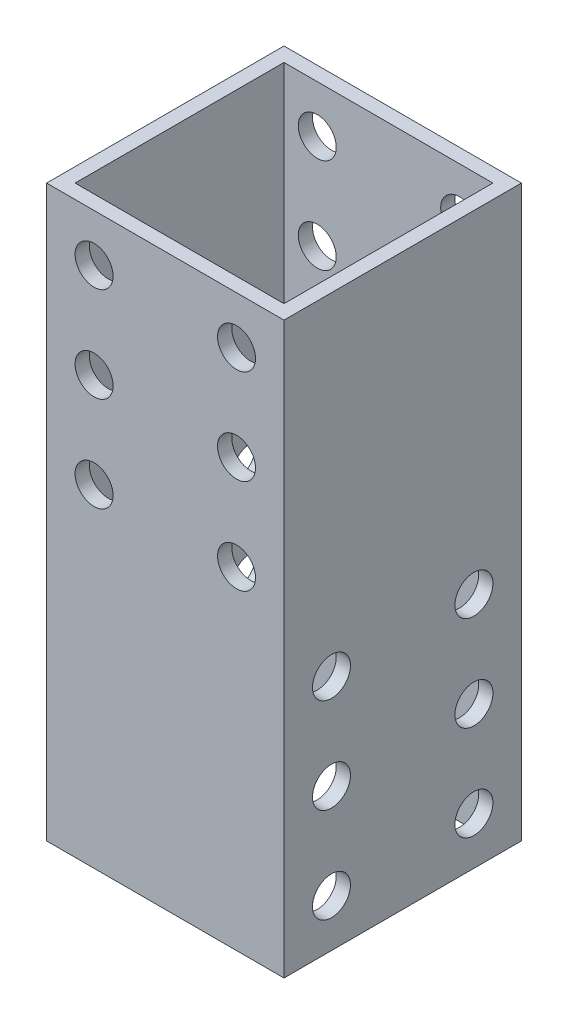
SolidWorks part; units mm, degrees
material "1060 Alloy"
ref_plane "Front Plane" through (0, 0, 0) normal (0, 0, 1) x (1, 0, 0)
ref_plane "Top Plane" through (0, 0, 0) normal (0, 1, 0) x (1, 0, 0)
ref_plane "Right Plane" through (0, 0, 0) normal (1, 0, 0) x (0, 0, -1)
sketch "Sketch3" plane through (0, 0, 0) normal (0, 1, 0) x (1, 0, 0)
  line L0 (0, 86.7063) -> (0, -87.1032) construction
  line L1 (-136.9048, 0) -> (130.9524, 0) construction
  line L7 (-12.5, 12.5) -> (12.5, 12.5)
  line L8 (-12.5, 12.5) -> (-12.5, -12.5)
  line L13 (-12.5, -12.5) -> (12.5, -12.5)
  line L14 (12.5, 12.5) -> (12.5, -12.5)
  line L15 (-12.5, 12.5) -> (12.5, -12.5) construction
  line L16 (-12.5, -12.5) -> (12.5, 12.5) construction
  line L17 (-11, 11) -> (11, 11)
  line L18 (-11, 11) -> (-11, -11)
  line L19 (-11, -11) -> (11, -11)
  line L20 (11, 11) -> (11, -11)
  line L21 (-11, 11) -> (11, -11) construction
  line L22 (-11, -11) -> (11, 11) construction
  point P5 (0, 0)
  point P10 (0, 0)
  dimension "D1" = 25
  dimension "D2" = 25
  dimension "D3" = 22
extrude "Boss-Extrude1" add sketch "Sketch3" along normal blind 30 and the other way blind 30
sketch "Sketch6" plane through (12.5, 0, 0) normal (1, 0, 0) x (0, 0, -1)
  line L0 (0, 0) -> (0, -102.9817) construction
  line L1 (-12.5, -30) -> (12.5, -30) construction
  circle A0 centre (7.5, -25) radius 2
  circle A1 centre (7.5, -5) radius 2
  circle A3 centre (-7.5, -25) radius 2
  circle A4 centre (-7.5, -5) radius 2
  circle A5 centre (7.5, -15) radius 2
  circle A6 centre (-7.5, -15) radius 2
  dimension "D2" = 10
  dimension "D9" = 10
  dimension "D3" = 7.5
  dimension "D4" = 7.5
  dimension "D5" = 7.5
  dimension "D6" = 7.5
  dimension "D7" = 5
  dimension "D8" = 10
  dimension "D10" = 5
  dimension "D11" = 10
  dimension "D12" = 7.5
  dimension "D13" = 7.5
extrude "Cut-Extrude3" cut sketch "Sketch6" against normal blind 25
sketch "Sketch7" plane through (0, 0, -12.5) normal (0, 0, -1) x (-1, 0, 0)
  line L0 (0, 0) -> (0, 70.1061) construction
  line L2 (-12.5, 30) -> (12.5, 30) construction
  circle A0 centre (7.5, 25) radius 2
  circle A1 centre (7.5, 15) radius 2
  circle A3 centre (-7.5, 25) radius 2
  circle A4 centre (-7.5, 15) radius 2
  circle A5 centre (-7.5, 5) radius 2
  circle A6 centre (7.5, 5) radius 2
  dimension "D1" = 7.5
  dimension "D5" = 10
  dimension "D2" = 7.5
  dimension "D3" = 7.5
  dimension "D4" = 7.5
  dimension "D6" = 10
  dimension "D7" = 5
  dimension "D8" = 10
  dimension "D9" = 7.5
  dimension "D10" = 5
  dimension "D11" = 7.5
  dimension "D12" = 10
extrude "Cut-Extrude4" cut sketch "Sketch7" against normal blind 25
